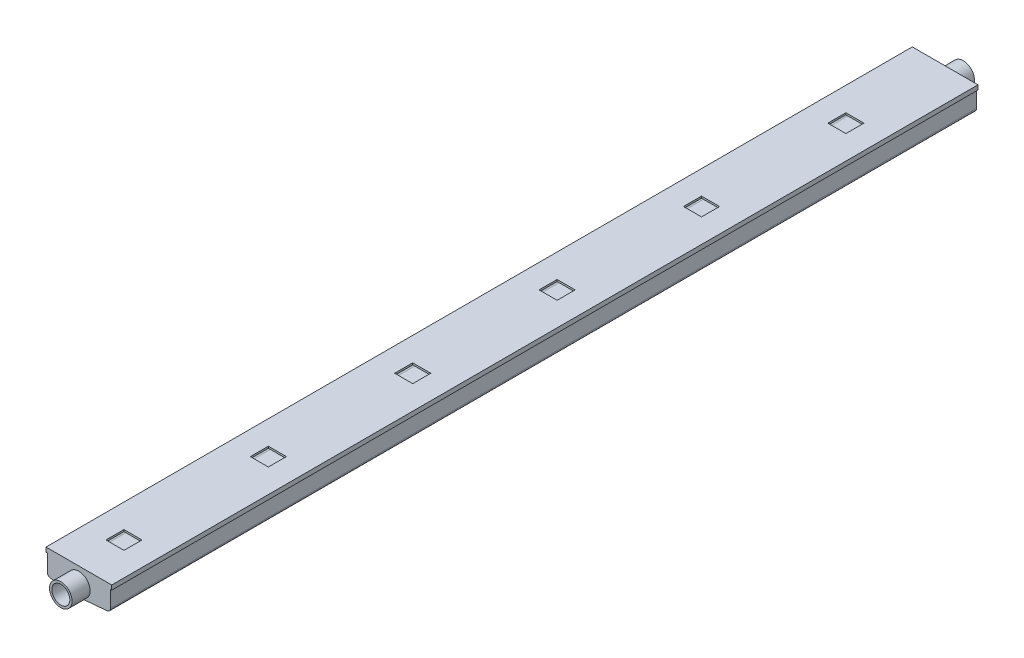
SolidWorks part; units mm, degrees
ref_plane "Front Plane" through (0, 0, 0) normal (0, 0, 1) x (1, 0, 0)
ref_plane "Top Plane" through (0, 0, 0) normal (0, 1, 0) x (1, 0, 0)
ref_plane "Right Plane" through (0, 0, 0) normal (1, 0, 0) x (0, 0, -1)
sketch "Sketch1" plane through (0, 0, 0) normal (0, 0, 1) x (1, 0, 0)
  line L0 (0, 0) -> (0, -36.8436) construction
  line L2 (-44.45, -17.145) -> (-44.45, 17.145)
  line L3 (-44.45, 17.145) -> (44.45, 17.145)
  line L4 (44.45, -17.145) -> (44.45, 17.145)
  line L5 (-44.45, -17.145) -> (44.45, 17.145) construction
  line L6 (-44.45, 17.145) -> (44.45, -17.145) construction
  line L7 (-44.45, -17.145) -> (0, -20.955)
  line L8 (0, -20.955) -> (44.45, -17.145)
  point P0 (0, 0)
  point P8 (0, 0)
  dimension "D1" = 88.9
  dimension "D2" = 34.29
  dimension "D3" = 38.1
extrude "Boss-Extrude1" add sketch "Sketch1" along normal blind 1219.2
sketch "Sketch3" plane through (-44.45, 0, 0) normal (-1, 0, 0) x (0, 0, 1)
  line L0 (1219.2, 17.145) -> (1219.2, -17.145) construction
  line L1 (0, 17.145) -> (1219.2, 17.145)
  line L2 (0, 17.145) -> (0, 10.795)
  line L3 (0, 10.795) -> (1219.2, 10.795)
  line L4 (1219.2, 17.145) -> (1219.2, 10.795)
  dimension "D1" = 6.35
extrude "Boss-Extrude2" add sketch "Sketch3" along normal blind 1.778
sketch "Sketch4" plane through (44.45, 0, 0) normal (1, 0, 0) x (0, 0, -1)
  line L0 (0, -17.145) -> (0, 17.145) construction
  line L1 (-1219.2, 17.145) -> (0, 17.145)
  line L2 (-1219.2, 17.145) -> (-1219.2, 10.795)
  line L3 (-1219.2, 10.795) -> (0, 10.795)
  line L4 (0, 17.145) -> (0, 10.795)
  dimension "D1" = 6.35
extrude "Boss-Extrude3" add sketch "Sketch4" along normal blind 1.778
fillet "Fillet1" radius 5.08 2 edges at (-44.45, -17.145, 609.6) (44.45, -17.145, 609.6)
shell "Shell1" thickness 2.54
sketch "Sketch6" plane through (0, 17.145, 0) normal (0, 1, 0) x (1, 0, 0)
  line L0 (46.228, -1219.2) -> (-46.228, -1219.2) construction
  line L1 (12.7, -1143) -> (-12.7, -1143)
  line L2 (12.7, -1143) -> (12.7, -1168.4)
  line L3 (12.7, -1168.4) -> (-12.7, -1168.4)
  line L4 (-12.7, -1143) -> (-12.7, -1168.4)
  line L5 (12.7, -1143) -> (-12.7, -1168.4) construction
  line L6 (12.7, -1168.4) -> (-12.7, -1143) construction
  line L8 (12.7, -939.8) -> (12.7, -965.2)
  line L9 (12.7, -939.8) -> (-12.7, -939.8)
  line L10 (-12.7, -939.8) -> (-12.7, -965.2)
  line L11 (12.7, -965.2) -> (-12.7, -965.2)
  line L12 (12.7, -736.6) -> (12.7, -762)
  line L13 (12.7, -736.6) -> (-12.7, -736.6)
  line L14 (-12.7, -736.6) -> (-12.7, -762)
  line L15 (12.7, -762) -> (-12.7, -762)
  line L16 (12.7, -533.4) -> (12.7, -558.8)
  line L17 (12.7, -533.4) -> (-12.7, -533.4)
  line L18 (-12.7, -533.4) -> (-12.7, -558.8)
  line L19 (12.7, -558.8) -> (-12.7, -558.8)
  line L20 (12.7, -330.2) -> (12.7, -355.6)
  line L21 (12.7, -330.2) -> (-12.7, -330.2)
  line L22 (-12.7, -330.2) -> (-12.7, -355.6)
  line L23 (12.7, -355.6) -> (-12.7, -355.6)
  line L24 (12.7, -127) -> (12.7, -152.4)
  line L25 (12.7, -127) -> (-12.7, -127)
  line L26 (-12.7, -127) -> (-12.7, -152.4)
  line L27 (12.7, -152.4) -> (-12.7, -152.4)
  point P0 (0, -1155.7)
  point P9 (0, -1219.2)
  point P10 (0, -1168.4)
  dimension "D1" = 25.4
  dimension "D3" = 50.8
extrude "Cut-Extrude1" cut sketch "Sketch6" against normal up to next
sketch "Sketch7" plane through (0, 0, 0) normal (0, 0, -1) x (-1, 0, 0)
  circle A0 centre (0, -5.08) radius 15.875
  circle A1 centre (0, -5.08) radius 12.7
  dimension "D1" = 31.75
  dimension "D2" = 25.4
extrude "Boss-Extrude4" add sketch "Sketch7" along normal blind 25.4
sketch "Sketch10" plane through (0, 0, 0) normal (0, 0, -1) x (-1, 0, 0)
  circle A1 centre (0, -5.08) radius 12.7
extrude "Cut-Extrude2" cut sketch "Sketch10" against normal up to next
sketch "Sketch11" plane through (0, 0, 1219.2) normal (0, 0, 1) x (1, 0, 0)
  circle A1 centre (0, -5.08) radius 15.875
  circle A2 centre (0, -5.08) radius 12.7
  dimension "D1" = 31.75
  dimension "D2" = 25.4
extrude "Boss-Extrude5" add sketch "Sketch11" along normal blind 25.4
sketch "Sketch12" plane through (0, 0, 1219.2) normal (0, 0, 1) x (1, 0, 0)
  circle A0 centre (0, -5.08) radius 12.7
extrude "Cut-Extrude3" cut sketch "Sketch12" against normal up to next
